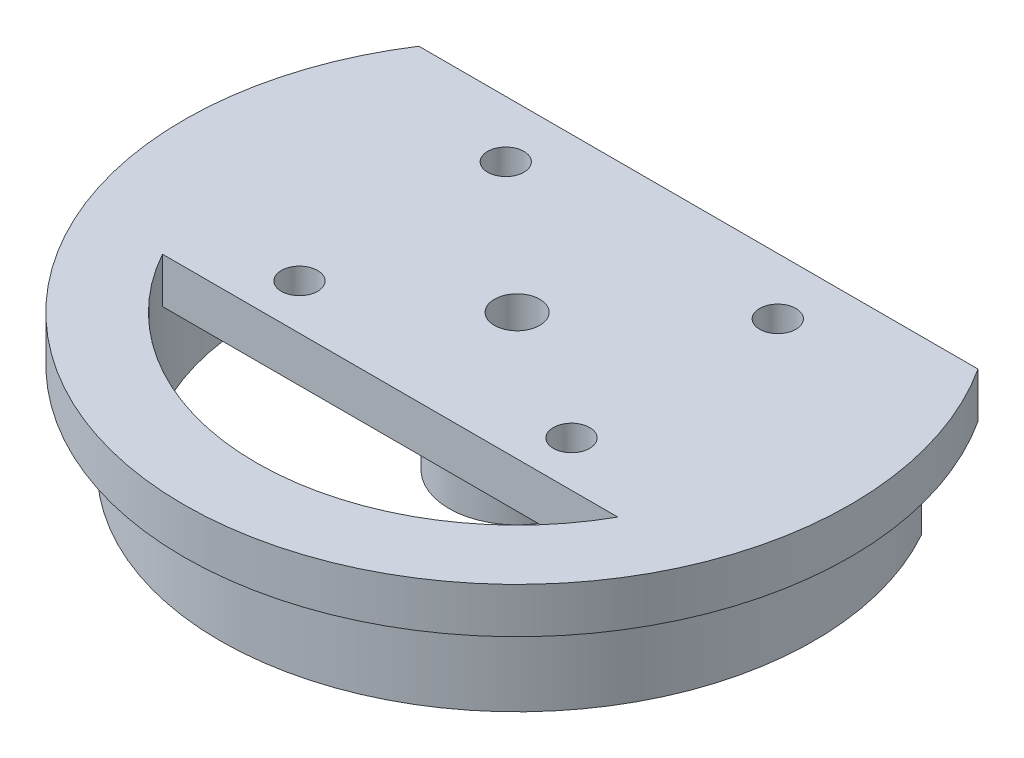
SolidWorks part; units mm, degrees
ref_plane "Спереди" through (0, 0, 0) normal (0, 0, 1) x (1, 0, 0)
ref_plane "Сверху" through (0, 0, 0) normal (0, 1, 0) x (1, 0, 0)
ref_plane "Справа" through (0, 0, 0) normal (1, 0, 0) x (0, 0, -1)
sketch "Эскиз1" plane through (0, 0, 0) normal (0, 1, 0) x (1, 0, 0)
  circle A0 centre (0, 0) radius 2.5
  circle A1 centre (0, 0) radius 7.5
  dimension "D1" = 15
  dimension "D2" = 5
extrude "cylinder" add sketch "Эскиз1" along normal blind 5 and the other way blind 10
sketch "Эскиз2" plane through (0, 0, 0) normal (0, 1, 0) x (1, 0, 0)
  circle A0 centre (0, 0) radius 36.75
  circle A1 centre (0, 0) radius 2.5
  dimension "D1" = 73.5
  dimension "D2" = 5
extrude "base horizont" add sketch "Эскиз2" along normal blind 5
sketch "Эскиз3" plane through (0, 5, 0) normal (0, 1, 0) x (1, 0, 0)
  circle A0 centre (0, 0) radius 28.75
  circle A1 centre (0, 0) radius 32.75
  dimension "D1" = 57.5
  dimension "D2" = 65.5
extrude "edge" add sketch "Эскиз3" against normal blind 15
sketch "Эскиз4" plane through (0, 5, 0) normal (0, 1, 0) x (1, 0, 0)
  line L0 (-10, 7.5) -> (10, 7.5) construction
  line L1 (-10, 2.5) -> (10, 2.5) construction
  line L2 (-10, 2.5) -> (-10, 20) construction
  line L3 (-10, 20) -> (10, 20) construction
  line L4 (10, 2.5) -> (10, 20) construction
  line L5 (-20, 20) -> (-10, 20) construction
  line L6 (10, 20) -> (20, 20) construction
  line L7 (20, 20) -> (20, 7.5) construction
  line L8 (20, 7.5) -> (-20, 7.5) construction
  line L9 (-20, 20) -> (-20, 7.5) construction
  circle A0 centre (-15, 13.75) radius 2
  circle A1 centre (0, 0) radius 2.5 construction
  circle A2 centre (15, 13.75) radius 2
  point P4 (0, 2.5)
  point P14 (-20, 13.75)
  point P19 (-15, 20)
  point P20 (15, 20)
  dimension "D6" = 4
  dimension "D1" = 20
  dimension "D2" = 20
  dimension "D3" = 12.5
  dimension "D4" = 10
  dimension "D5" = 40
sketch "Эскиз8" plane through (0, 0, 0) normal (0, 1, 0) x (1, 0, 0)
  line L1 (-30.8312, 36.75) -> (30.8312, 36.75)
  line L2 (-30.8312, 36.75) -> (-30.8312, 20)
  line L3 (-30.8312, 20) -> (30.8312, 20)
  line L4 (30.8312, 36.75) -> (30.8312, 20)
  circle A1 centre (0, 0) radius 36.75 construction
  dimension "D1" = 20
sketch "Эскиз10" plane through (0, 5, 0) normal (0, 1, 0) x (1, 0, 0)
  line L0 (0, -14) -> (45.2157, -14) construction
  line L1 (-25.111, -14) -> (25.111, -14)
  arc A0 (-25.111, -14) -> (25.111, -14) centre (0, 0) ccw
  circle A6 centre (0, 0) radius 28.75 construction
  dimension "D1" = 14
extrude "pie" cut sketch "Эскиз10" against normal up to next
sketch "Эскиз11" plane through (0, 5, 0) normal (0, 1, 0) x (1, 0, 0)
  line L0 (-10, -7.8) -> (-10, -14) construction
  line L1 (25.111, -14) -> (-25.111, -14) construction
  line L2 (-10, -14) -> (-4.1, -14) construction
  line L3 (-4.1, -14) -> (-4.1, -7.8) construction
  line L4 (-4.1, -7.8) -> (-10, -7.8) construction
  line L6 (0, 0) -> (0, -14) construction
  line L7 (4.1, -7.8) -> (10, -7.8) construction
  line L8 (4.1, -14) -> (4.1, -7.8) construction
  line L9 (10, -14) -> (4.1, -14) construction
  line L10 (10, -7.8) -> (10, -14) construction
  line L12 (-4.1, -7.8) -> (4.1, -7.8) construction
  line L13 (10, -14) -> (20, -14) construction
  line L14 (10, -14) -> (10, -4) construction
  line L15 (10, -4) -> (20, -4) construction
  line L16 (20, -14) -> (20, -4) construction
  line L17 (-10, -14) -> (-20, -14) construction
  line L18 (-10, -14) -> (-10, -4) construction
  line L19 (-10, -4) -> (-20, -4) construction
  line L20 (-20, -14) -> (-20, -4) construction
  circle A0 centre (-15, -9) radius 2
  circle A1 centre (15, -9) radius 2
  point P20 (15, -4)
  point P21 (-20, -9)
  point P22 (-15, -4)
  dimension "D6" = 4
  dimension "D1" = 6.2
  dimension "D2" = 8.2
  dimension "D3" = 20
  dimension "D4" = 10
  dimension "D5" = 10
extrude "cutoff" cut sketch "Эскиз8" against normal blind 10 and the other way blind 10
extrude "main horns holes" cut sketch "Эскиз4" against normal up to next
extrude "minor horns holes" cut sketch "Эскиз11" against normal up to next
sketch "Эскиз12" plane through (0, -10, 0) normal (0, -1, 0) x (1, 0, 0)
  line L0 (20.6534, -20) -> (-20.6534, -20) construction
  line L1 (-28.5756, -16) -> (-20.5756, -16)
  line L2 (-28.5756, -16) -> (-28.5756, -20)
  line L3 (-28.5756, -20) -> (-20.5756, -20)
  line L4 (-20.5756, -16) -> (-20.5756, -20)
  line L6 (28.5756, -16) -> (20.5756, -16)
  line L7 (28.5756, -16) -> (28.5756, -20)
  line L8 (28.5756, -20) -> (20.5756, -20)
  line L9 (20.5756, -16) -> (20.5756, -20)
  arc A0 (25.9338, -20) -> (-25.9338, -20) centre (0, 0) ccw construction
  dimension "D1" = 4
  dimension "D2" = 8
extrude "Вытянуть1" cut sketch "Эскиз12" against normal blind 10
